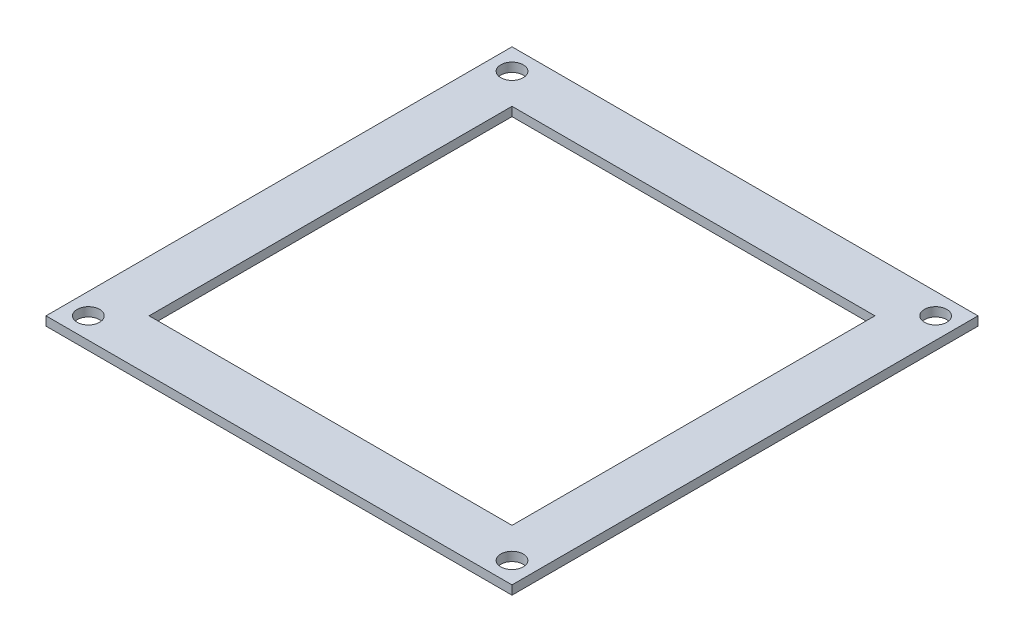
SolidWorks part; units mm, degrees
ref_plane "Front Plane" through (0, 0, 0) normal (0, 0, 1) x (1, 0, 0)
ref_plane "Top Plane" through (0, 0, 0) normal (0, 1, 0) x (1, 0, 0)
ref_plane "Right Plane" through (0, 0, 0) normal (1, 0, 0) x (0, 0, -1)
sketch "Sketch1" plane through (0, 0, 0) normal (0, 1, 0) x (1, 0, 0)
  line L1 (-30, 30) -> (30, 30) construction
  line L2 (-30, 30) -> (-30, -30) construction
  line L3 (-30, -30) -> (30, -30) construction
  line L4 (30, 30) -> (30, -30) construction
  line L5 (0, -30) -> (0, 30) construction
  line L6 (-30, 0) -> (30, 0) construction
  line L7 (-25.7, 25.7) -> (25.7, 25.7)
  line L8 (-25.7, 25.7) -> (-25.7, -25.7)
  line L9 (-25.7, -25.7) -> (25.7, -25.7)
  line L10 (25.7, 25.7) -> (25.7, -25.7)
  line L11 (0, -25.7) -> (0, 25.7) construction
  line L12 (-25.7, 0) -> (25.7, 0) construction
  line L13 (-33, 33) -> (33, 33)
  line L14 (-33, 33) -> (-33, -33)
  line L15 (-33, -33) -> (33, -33)
  line L16 (33, 33) -> (33, -33)
  line L17 (0, -33) -> (0, 33) construction
  line L18 (-33, 0) -> (33, 0) construction
  circle A0 centre (-30, 30) radius 1.59
  circle A1 centre (30, 30) radius 1.59
  circle A2 centre (30, -30) radius 1.59
  circle A3 centre (-30, -30) radius 1.59
  point P0 (0, 0)
  point P9 (0, 0)
  point P13 (0, 0)
  dimension "D1" = 3.18
  dimension "D2" = 60
  dimension "D3" = 51.4
  dimension "D4" = 3
  dimension "D5" = 3
  dimension "D6" = 66
extrude "Boss-Extrude1" add sketch "Sketch1" along normal blind 1.27
equation "\"Lens_dim\"= 50.8"
equation "\"D3@Sketch1\"=\"Lens_dim\" +0.3*2"
equation "\"D5@Sketch1\"=\"D4@Sketch1\""
